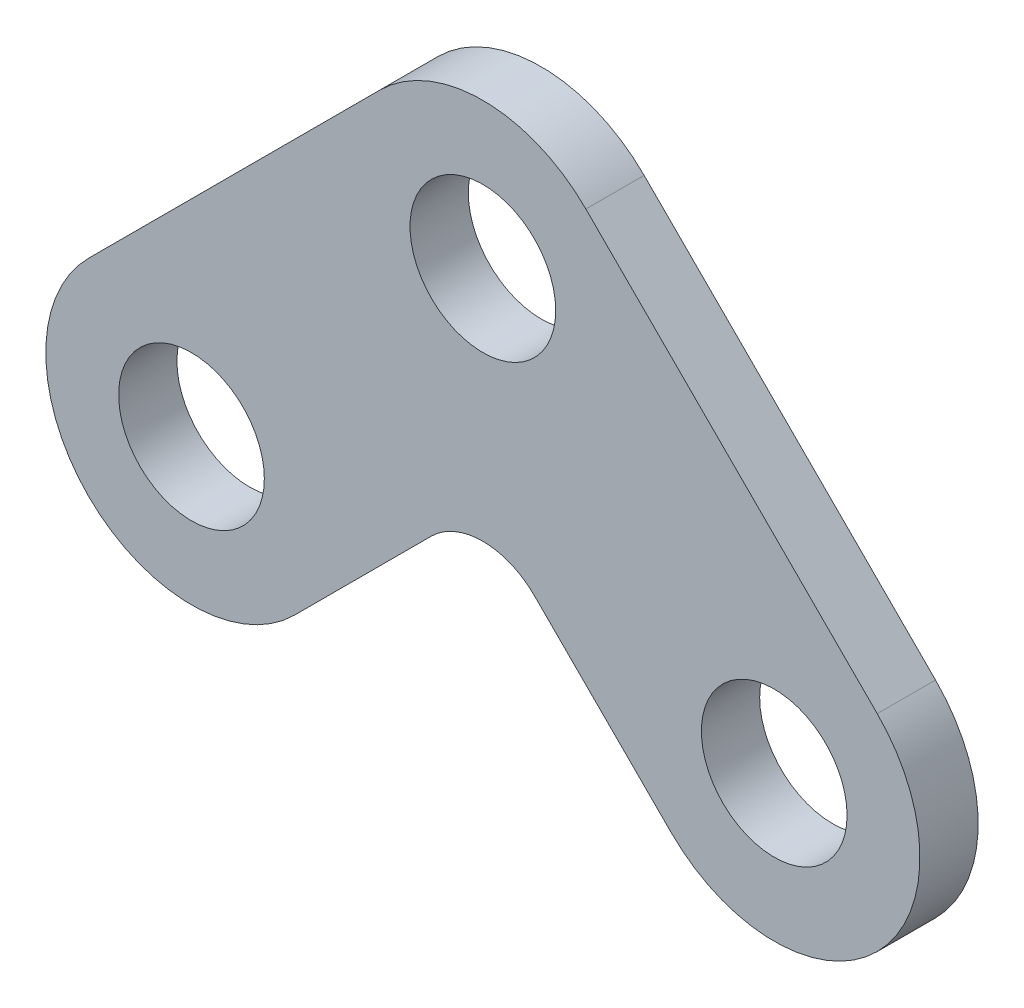
SolidWorks part; units mm, degrees
ref_plane "前视基准面" through (0, 0, 0) normal (0, 0, 1) x (1, 0, 0)
ref_plane "上视基准面" through (0, 0, 0) normal (0, 1, 0) x (1, 0, 0)
ref_plane "右视基准面" through (0, 0, 0) normal (1, 0, 0) x (0, 0, -1)
sketch "草图1" plane through (0, 0, 0) normal (0, 0, 1) x (1, 0, 0)
  line L0 (-7.0711, 7.0711) -> (-27.0711, -12.9289)
  line L1 (0, -14.1421) -> (-12.9289, -27.0711)
  line L2 (0, 28.389) -> (0, 10) construction
  line L3 (0, -14.1421) -> (12.9289, -27.0711)
  line L4 (7.0711, 7.0711) -> (27.0711, -12.9289)
  line L5 (0, -10) -> (0, -43.6001) construction
  arc A0 (7.0711, 7.0711) -> (-7.0711, 7.0711) centre (0, 0) ccw
  arc A1 (-27.0711, -12.9289) -> (-12.9289, -27.0711) centre (-20, -20) ccw
  arc A2 (27.0711, -12.9289) -> (12.9289, -27.0711) centre (20, -20) cw
  dimension "D1" = 20
  dimension "D2" = 20
  dimension "D3" = 20
  dimension "D4" = 20
base flange "基体-法兰1" sketch "草图1" thickness 4 reverse thickness direction no parameters "D1"=0.7366
sketch "草图6" plane through (0, 0, 0) normal (0, 0, 1) x (1, 0, 0)
  circle A0 centre (0, 0) radius 5
  circle A1 centre (-20, -20) radius 5
  circle A2 centre (20, -20) radius 5
  dimension "D1" = 10
  dimension "D3" = 10
  dimension "D4" = 10
extrude "切除-拉伸1" cut sketch "草图6" against normal blind 10 normal cut yes
fillet "圆角1" radius 5 1 edges at (0, -14.1421, -2)
sketch "折弯-线1" [suppressed] plane through (0, 0, 0) normal (0, 1, 0) x (1, 0, 0)
sketch "边界框1" [suppressed] plane through (0, 0, 0) normal (0, 1, 0) x (1, 0, 0)
sheet metal parameters "钣金1" thickness 4 parameters "D1"=0.7366
flat pattern "平板型式1" [suppressed]
sketch "折弯-线2" plane through (0, 0, 0) normal (0, 1, 0) x (1, 0, 0)
sketch3d "边界框2" [suppressed]
  line L0 (20, -34.1421, 0) -> (-14.1421, 0, 0) construction
  line L1 (54.1421, 0, 0) -> (20, 34.1421, 0) construction
  line L2 (20, -34.1421, 0) -> (54.1421, 0, 0) construction
  line L3 (-14.1421, 0, 0) -> (20, 34.1421, 0) construction
sheet metal parameters "钣金2" thickness 4 parameters "D1"=0.7366
flat pattern "平板型式1"
sketch "折弯-线2" plane through (0, 0, 0) normal (0, 1, 0) x (1, 0, 0)
sketch3d "边界框2" [suppressed]
  line L0 (-20, -34.1421, 0) -> (14.1421, 0, 0) construction
  line L1 (-54.1421, 0, 0) -> (-20, 34.1421, 0) construction
  line L2 (-20, -34.1421, 0) -> (-54.1421, 0, 0) construction
  line L3 (14.1421, 0, 0) -> (-20, 34.1421, 0) construction
